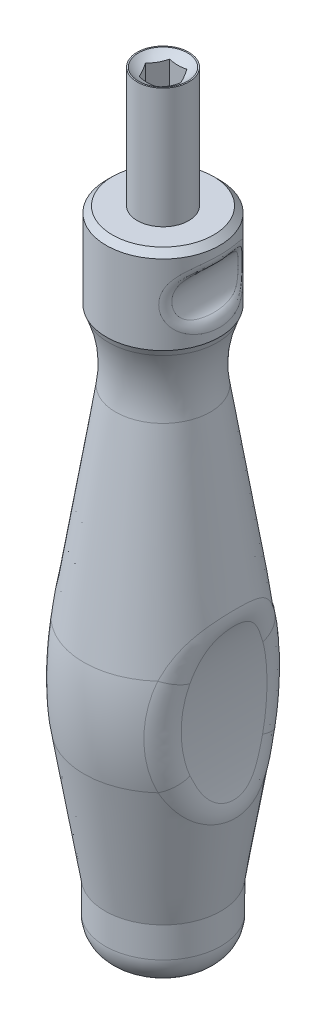
SolidWorks part; units mm, degrees
ref_plane "Front Plane" through (0, 0, 0) normal (0, 0, 1) x (1, 0, 0)
ref_plane "Top Plane" through (0, 0, 0) normal (0, 1, 0) x (1, 0, 0)
ref_plane "Right Plane" through (0, 0, 0) normal (1, 0, 0) x (0, 0, -1)
sketch "Sketch1" plane through (0, 0, 0) normal (0, 1, 0) x (1, 0, 0)
  line L1 (2.8868, 0) -> (1.4434, 2.5)
  line L2 (1.4434, 2.5) -> (-1.4434, 2.5)
  line L3 (-1.4434, 2.5) -> (-2.8868, 0)
  line L4 (-2.8868, 0) -> (-1.4434, -2.5)
  line L5 (-1.4434, -2.5) -> (1.4434, -2.5)
  line L6 (1.4434, -2.5) -> (2.8868, 0)
  circle A0 centre (0, 0) radius 2.5 construction
  circle A1 centre (0, 0) radius 4.2558
  dimension "D1" = 5
extrude "Boss-Extrude1" add sketch "Sketch1" against normal blind 20
sketch "Sketch2" plane through (0, -20, 0) normal (0, -1, 0) x (1, 0, 0)
  circle A0 centre (0, 0) radius 7
sketch "Sketch3" plane through (0, 0, 0) normal (0, 0, 1) x (1, 0, 0)
  line L0 (0, -20) -> (0, -120)
  line L1 (-7, -20) -> (7, -20) construction
  line L2 (0, -20) -> (8.3443, -20)
  line L3 (9.3443, -21) -> (9.3443, -34.0796)
  line L4 (9.3443, -34.0796) -> (8.9567, -35.0594)
  line L5 (7.8035, -45.5636) -> (13.076, -78.6527)
  line L6 (13.0392, -94.6153) -> (9.5386, -115.9526)
  line L7 (9.5386, -115.9526) -> (0, -115.9526)
  line L8 (8.3443, -20) -> (9.3443, -21)
  arc A0 (13.076, -78.6527) -> (13.0392, -94.6153) centre (-36.3011, -86.5204) cw
  arc A1 (8.9567, -35.0594) -> (7.8035, -45.5636) centre (27.5544, -42.4165) ccw
  point P6 (9.3443, -20)
  dimension "D2" = 50
  dimension "D5" = 20
  dimension "D1" = 100
  dimension "D3" = 95.9526
  dimension "D4" = 13.0796
revolve "Revolve1" add sketch "Sketch3" angle 360 about L0 region at (5.5081, -71.2507, 0)
ref_plane "Plane1" through (0, -120.9526, 0) normal (0, -1, 0) x (-1, 0, 0)
sketch "Sketch4" plane through (0, -120.9526, 0) normal (0, -1, 0) x (-1, 0, 0)
  circle A1 centre (0, 0) radius 9.5386
  circle A2 centre (0, 0) radius 9.5386 construction
extrude "Boss-Extrude2" add sketch "Sketch4" along normal blind 5 separate body
fillet "Fillet1" radius 5 1 edges at (9.5386, -125.9526, 0)
loft "Loft1" add section face at (9.5386, -120.9526, 0) section face at (-9.5386, -115.9526, 0) connector at (-9.5162, -120.9526, -0.6528) connector at (-9.5048, -115.9526, 0.8022)
sketch "Sketch5" plane through (0, 0, 0) normal (0, 0, 1) x (1, 0, 0)
  line L0 (9.3443, -34.0796) -> (9.3443, -21) construction
  line L1 (0, 0) -> (0, -50000) construction
  line L2 (-4.5386, -125.9526) -> (4.5386, -125.9526) construction
  arc A0 (13.0392, -94.6153) -> (13.076, -78.6527) centre (-36.3011, -86.5204) ccw construction
  ellipse E0 centre (9.3443, -27.5398) end of major axis (9.3443, -31.298) minor radius 2.4362
  ellipse E1 centre (-9.3443, -27.5398) end of major axis (-9.3443, -23.7817) minor radius 2.4362
  ellipse E2 centre (13.6987, -86.6355) end of major axis (13.6987, -71.7332) minor radius 3.6326
  ellipse E3 centre (-13.6987, -86.6355) end of major axis (-13.6987, -71.7332) minor radius 3.6326
  point P13 (0, -125.9526)
extrude "Cut-Extrude1" cut sketch "Sketch5" against normal through all and the other way through all
fillet "Fillet2" radius 5 8 edges at (-12.1355, -100.0874, 0.3796) (-10.0731, -85.7112, -9.2742) (-12.1441, -73.1669, 1.1857) (12.1858, -73.0872, 0.2858) (10.0663, -86.7653, -9.2905) (12.104, -100.0249, 1.0764) (-10.0708, -87.394, 9.2751) (10.0703, -85.9226, 9.2817)
fillet "Fillet3" radius 2 2 edges at (-8.7176, -23.9081, -3.3645) (9.32, -31.2978, 0.6742)
sketch "Sketch6" plane through (0, 0, 0) normal (0, 0, 1) x (1, 0, 0)
  line L1 (4.2558, 0) -> (-4.2558, 0) construction
  line L2 (4.0459, -0.2) -> (4.2558, -0.2)
  line L3 (0, 0) -> (0, -1.7628)
  line L4 (0, 0) -> (4.2558, 0)
  line L5 (4.2558, 0) -> (4.2558, -0.2)
  line L6 (4.2558, -20) -> (4.2558, 0) construction
  arc A0 (0, -1.7628) -> (4.0459, -0.2) centre (0, 4.2558) ccw
revolve "Cut-Revolve1" cut sketch "Sketch6" angle 360 about L3 region at (1.6426, -0.7125, 0)
